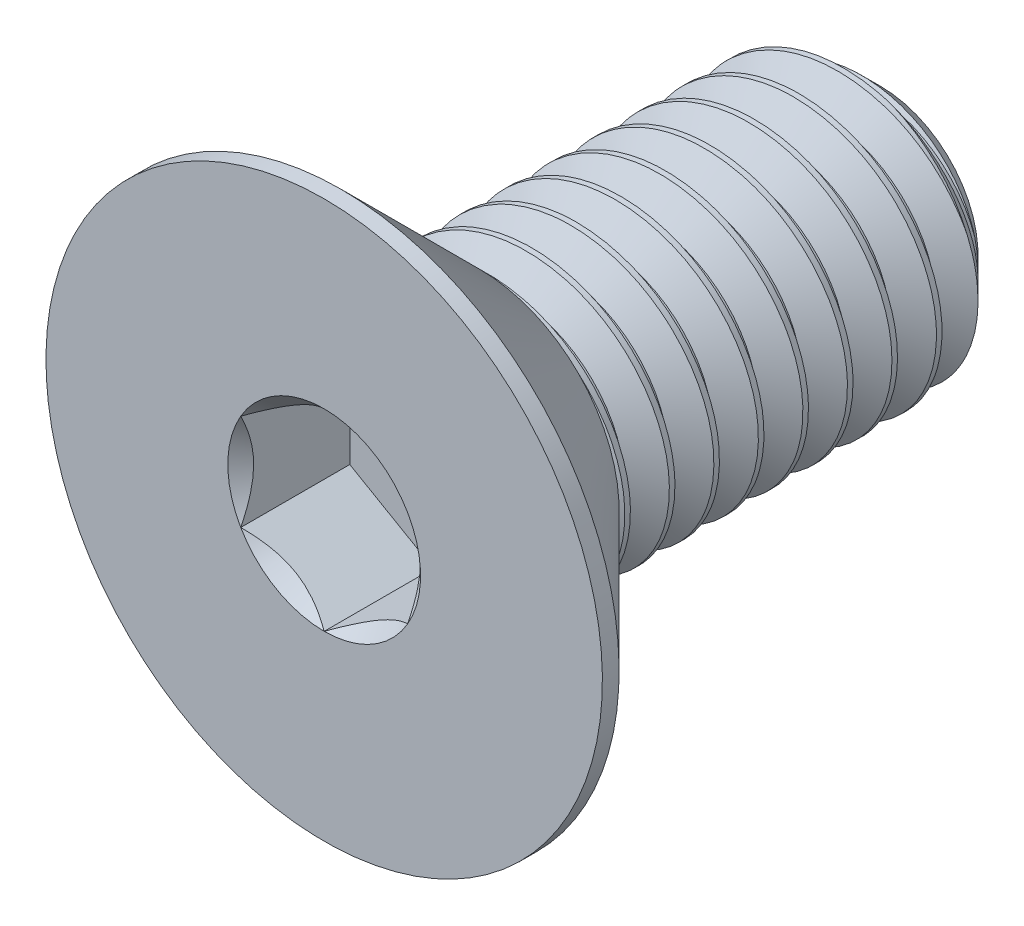
SolidWorks part; units mm, degrees
ref_plane "Front" through (0, 0, 0) normal (0, 0, 1) x (1, 0, 0)
ref_plane "Top" through (0, 0, 0) normal (0, 1, 0) x (1, 0, 0)
ref_plane "Right" through (0, 0, 0) normal (1, 0, 0) x (0, 0, -1)
sketch "Sketch1" plane through (0, 0, 0) normal (1, 0, 0) x (0, 0, -1)
  line L0 (-5, 5) -> (-4.7, 5) construction
  line L1 (-4.7, 5) -> (-2.2, 2.5) construction
  line L2 (-5, 2.5) -> (5, 2.5) construction
  line L3 (5, 2.5) -> (5, 0) construction
  line L4 (5, 0) -> (-5, 0) construction
  line L5 (-5, 0) -> (-5, 5) construction
  line L6 (-5, 5) -> (-5, -5) construction
  line L7 (5, 2.5) -> (5, -2.5) construction
  line L8 (-5, -5) -> (-4.7, -5) construction
  line L9 (-4.7, -5) -> (-2.2, -2.5) construction
  line L11 (-5, 2.5) -> (-5, 0) construction
  line L12 (-2.2, 2.5) -> (-2.2, 0) construction
  line L13 (4.95, 2.5866) -> (5.35, 1.8938) construction
  line L14 (5.35, 1.8938) -> (5.75, 2.5866) construction
  line L15 (5.75, 2.5866) -> (4.95, 2.5866) construction
  line L16 (5.35, 2.5866) -> (5.35, 2.5) construction
  line L17 (5.35, 2.5) -> (5.35, 1.9804) construction
  line L18 (5.35, 1.9804) -> (5.35, 1.8938) construction
  line L19 (5.35, 2.5433) -> (5.725, 2.5433) construction
  line L20 (5.35, 2.5433) -> (4.975, 2.5433) construction
  line L21 (5, 2.5) -> (5.7, 2.5) construction
  line L22 (5.3, 1.9804) -> (5.4, 1.9804) construction
  line L23 (5, -2.5) -> (-2.2, -2.5) construction
  point P10 (3, -2.5)
  point P24 (-2.2, 2.5)
  point P30 (0, 0)
  dimension "Head Diameter" = 10
  dimension "Head Height" = 2.8
  dimension "Length" = 10
  dimension "Countersink Angle" = 90
  dimension "Thread Pitch" = 0.8
  dimension "D2" = 0.1
  dimension "Thread Size" = 5
  dimension "D1" = 2
sketch "Sketch2" plane through (0, 0, 0) normal (0, 0, 1) x (1, 0, 0)
  line L1 (0, 1.7321) -> (-1.5, 0.866) construction
  line L2 (-1.5, 0.866) -> (-1.5, -0.866) construction
  line L3 (-1.5, -0.866) -> (0, -1.7321) construction
  line L4 (0, -1.7321) -> (1.5, -0.866) construction
  line L5 (1.5, -0.866) -> (1.5, 0.866) construction
  line L6 (1.5, 0.866) -> (0, 1.7321) construction
  circle A0 centre (0, 0) radius 1.5 construction
  dimension "Drive Size" = 3
sketch "Sketch3" plane through (0, 0, 0) normal (1, 0, 0) x (0, 0, -1)
  line L0 (-5, 2.5) -> (5, 2.5)
  line L1 (5, 2.5) -> (5, 0)
  line L2 (5, 0) -> (-5, 0)
  line L3 (-5, 0) -> (-5, 2.5)
revolve "Revolve1" add sketch "Sketch3" angle 360 about L4
chamfer "Chamfer1" distance 0.75 angle 45 1 edges at (0, 2.5, -5)
sketch "Sketch6" plane through (0, 0, 0) normal (1, 0, 0) x (0, 0, -1)
  line L0 (-5, 5) -> (-4.7, 5)
  line L1 (-4.7, 5) -> (-2.2, 2.5)
  line L2 (-2.2, 2.5) -> (-2.2, 0)
  line L3 (-2.2, 0) -> (-5, 0)
  line L4 (-5, 0) -> (-5, 5)
revolve "Revolve2" add sketch "Sketch6" angle 360 about L4
sketch "Sketch8" plane through (0, 0, 5) normal (0, 0, 1) x (1, 0, 0)
  line L0 (0, 1.7321) -> (-1.5, 0.866) construction
  line L1 (1.5, 0.866) -> (0, 1.7321) construction
  line L2 (1.5, -0.866) -> (1.5, 0.866) construction
  line L3 (0, -1.7321) -> (1.5, -0.866) construction
  line L4 (-1.5, 0.866) -> (-1.5, -0.866) construction
  line L5 (-1.5, -0.866) -> (0, -1.7321) construction
  line L6 (0, 1.7321) -> (-1.5, 0.866)
  line L7 (1.5, 0.866) -> (0, 1.7321)
  line L8 (1.5, -0.866) -> (1.5, 0.866)
  line L9 (0, -1.7321) -> (1.5, -0.866)
  line L10 (-1.5, 0.866) -> (-1.5, -0.866)
  line L11 (-1.5, -0.866) -> (0, -1.7321)
extrude "Cut-Extrude1" cut sketch "Sketch8" against normal blind 1.96
sketch "Sketch9" plane through (0, 0, 5) normal (0, 0, 1) x (1, 0, 0)
  circle A0 centre (0, 0) radius 1.7321
extrude "Cut-Extrude2" cut sketch "Sketch9" against normal up to next (1.96 mm away) draft 45
ref_plane "Plane1" through (0, 0, 2.2) normal (0, 0, 1) x (1, 0, 0)
split "Split1" trim tools "Plane1" bodies to split 124 resulting bodies 126 127
sketch "Sketch4" plane through (0, 0, -5) normal (0, 0, -1) x (-1, 0, 0)
  circle A0 centre (0, 0) radius 2.5 construction
  circle A1 centre (0, 0) radius 2.5
curve "Helix/Spiral1" pitch 0.8 height 10 turns 12.5
sketch "Sketch10" plane through (0, 0, 0) normal (1, 0, 0) x (0, 0, -1)
  line L0 (4.975, 2.5433) -> (5.725, 2.5433)
  line L1 (5.725, 2.5433) -> (5.4, 1.9804)
  line L2 (5.4, 1.9804) -> (5.3, 1.9804)
  line L3 (5.3, 1.9804) -> (4.975, 2.5433)
sweep "Cut-Sweep1" cut profiles "Sketch10" path "Helix/Spiral1" align with end faces yes
combine bodies "Combine1" operation type add bodies to combine 130 126
equation "\"D2@Sketch1\" = \"Thread Pitch@Sketch1\" / 8"
equation "\"D4@Helix/Spiral1\"=\"Thread Pitch@Sketch1\""
equation "\"D1@Chamfer1\"=\"Thread Size@Sketch1\"*.15"
equation "\"D1@Cut-Extrude1\"=\"Head Height@Sketch1\"*.7"
equation "\"D1@Sketch1\"=\"Thread Pitch@Sketch1\"*2.5"
equation "\"D3@Helix/Spiral1\"=\"Length@Sketch1\""
